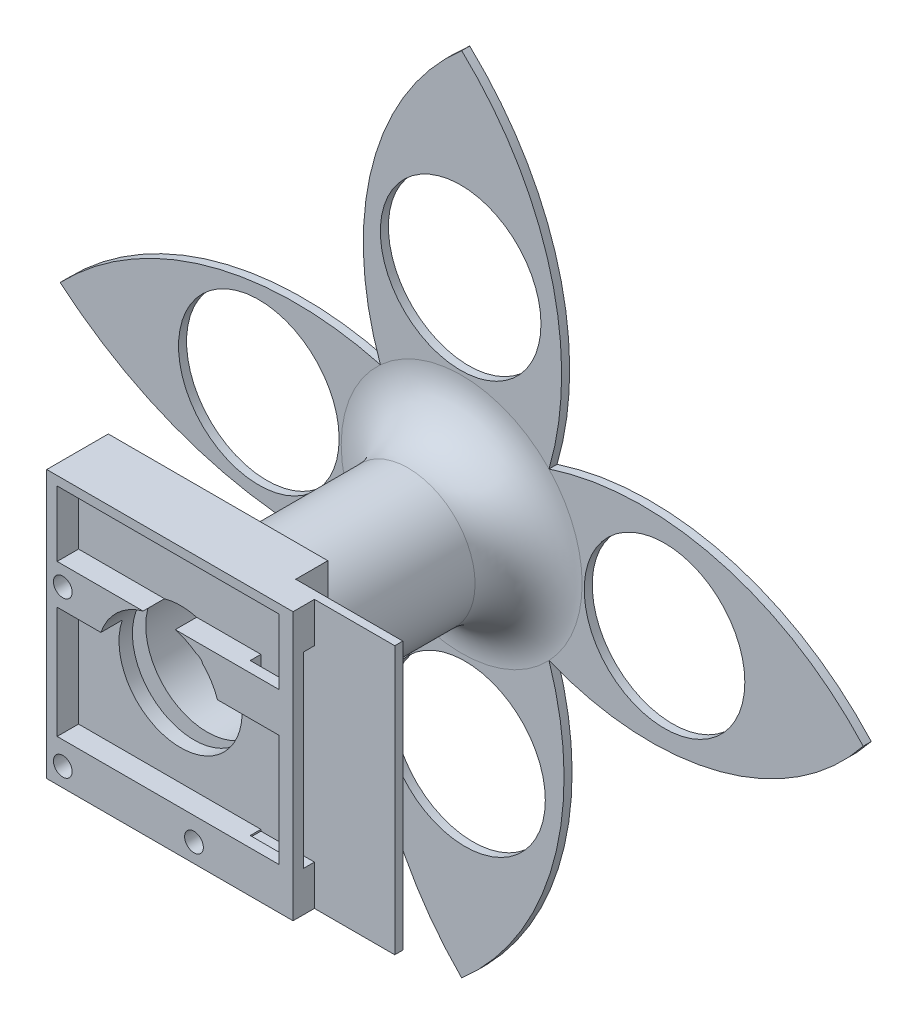
SolidWorks part; units mm, degrees
ref_plane "前视基准面" through (0, 0, 0) normal (0, 0, 1) x (1, 0, 0)
ref_plane "上视基准面" through (0, 0, 0) normal (0, 1, 0) x (1, 0, 0)
ref_plane "右视基准面" through (0, 0, 0) normal (1, 0, 0) x (0, 0, -1)
other "Configuration Table"
sketch "草图1" plane through (0, 0, 0) normal (0, 0, 1) x (1, 0, 0)
  circle A0 centre (0, 0) radius 150
extrude "凸台-拉伸1" add sketch "草图1" along normal blind 3
sketch "草图2" plane through (0, 0, 3) normal (0, 0, 1) x (1, 0, 0)
  circle A0 centre (0, 0) radius 25
extrude "凸台-拉伸2" add sketch "草图2" along normal blind 90
sketch "草图4" plane through (0, 0, 93) normal (0, 0, 1) x (1, 0, 0)
  line L3 (-40, -40) -> (40, -40)
  line L6 (40, 40) -> (-40, 40)
  line L7 (-40, 40) -> (-40, -40)
  line L8 (40, 40) -> (40, -40)
extrude "凸台-拉伸3" add sketch "草图4" along normal blind 5
sketch "草图5" plane through (0, 0, 98) normal (0, 0, 1) x (1, 0, 0)
  line L0 (-40, -40) -> (-40, -36)
  line L5 (-40, -36) -> (40, -36)
  line L16 (-40, 40) -> (-40, 36)
  line L17 (-40, 40) -> (-40, -40) construction
  line L18 (-40, 36) -> (40, 36)
  line L19 (40, 36) -> (40, 40)
  line L20 (40, 40) -> (-40, 40)
  line L21 (40, -36) -> (40, -40)
  line L22 (40, -40) -> (-40, -40)
extrude "凸台-拉伸4" add sketch "草图5" along normal blind 5
sketch "草图6" plane through (0, 0, 103) normal (0, 0, 1) x (1, 0, 0)
  line L1 (-40, 40) -> (40, 40)
  line L2 (-40, 40) -> (-40, -40)
  line L3 (-40, -40) -> (40, -40)
  line L4 (40, 40) -> (40, -40)
extrude "凸台-拉伸5" add sketch "草图6" along normal blind 5
sketch "草图8" plane through (0, -40, 0) normal (0, -1, 0) x (1, 0, 0)
  line L6 (-40, 93) -> (40, 93)
  line L7 (40, 93) -> (40, 108)
  line L10 (40, 108) -> (-40, 108)
  line L11 (-40, 108) -> (-40, 93)
  line L12 (-40, 93) -> (40, 93)
  line L13 (40, 93) -> (40, 108)
  line L16 (40, 108) -> (-40, 108)
  line L17 (-40, 108) -> (-40, 93)
  dimension "D1" = 0
extrude "凸台-拉伸7" add sketch "草图8" along normal blind 10
sketch "草图9" plane through (0, 40, 0) normal (0, 1, 0) x (1, 0, 0)
  line L6 (40, -93) -> (-40, -93)
  line L7 (-40, -93) -> (-40, -108)
  line L8 (-40, -108) -> (40, -108)
  line L11 (40, -108) -> (40, -93)
  line L12 (40, -93) -> (-40, -93)
  line L13 (-40, -93) -> (-40, -108)
  line L14 (-40, -108) -> (40, -108)
  line L17 (40, -108) -> (40, -93)
  dimension "D1" = 0
extrude "凸台-拉伸8" add sketch "草图9" along normal blind 10
sketch "草图10" plane through (0, 0, 108) normal (0, 0, 1) x (1, 0, 0)
  line L2 (-40, -50) -> (-40, 50)
  line L5 (-40, -50) -> (50, -50)
  line L6 (50, -50) -> (50, 50)
  line L7 (-40, 50) -> (40, 50) construction
  line L8 (50, 50) -> (-40, 50)
extrude "凸台-拉伸9" add sketch "草图10" along normal blind 8
sketch "草图11" plane through (0, 0, 116) normal (0, 0, 1) x (1, 0, 0)
  circle A0 centre (-36, 15) radius 3.5
  circle A1 centre (-36, -43) radius 3.5
  circle A2 centre (13, 15) radius 3.5
  circle A3 centre (13, -43) radius 3.5
extrude "切除-拉伸1" cut sketch "草图11" against normal blind 9
sketch "草图12" plane through (-40, 0, 0) normal (-1, 0, 0) x (0, 0, 1)
  line L0 (103, -36) -> (103, 36)
  line L1 (103, 36) -> (98, 36)
  line L2 (98, 36) -> (98, -36)
  line L3 (98, -36) -> (103, -36)
  line L4 (93, 50) -> (93, -50)
  line L5 (93, -50) -> (116, -50)
  line L6 (116, -50) -> (116, 50)
  line L7 (116, 50) -> (93, 50)
  line L8 (93, 50) -> (93, -50)
  line L9 (93, -50) -> (116, -50)
  line L10 (116, -50) -> (116, 50)
  line L11 (116, 50) -> (93, 50)
  dimension "D1" = 0
extrude "凸台-拉伸11" add sketch "草图12" along normal blind 2
sketch "草图17" plane through (0, 0, 3) normal (0, 0, 1) x (1, 0, 0)
  circle A0 centre (-75.7736, 1.5615) radius 30
  circle A1 centre (-0.3761, 76.3734) radius 30
  circle A2 centre (75.7702, -1.4084) radius 30
  circle A3 centre (1.2423, -76.8609) radius 30
extrude "切除-拉伸5" cut sketch "草图17" against normal blind 10 contours A1 | A0 | A2 | A3
sketch "草图18" plane through (0, 0, 116) normal (0, 0, 1) x (1, 0, 0)
  line L1 (-38.1119, 46.6223) -> (44.7722, 46.6223)
  line L2 (-38.1119, 46.6223) -> (-38.1119, 22.2011)
  line L3 (-38.1119, 22.2011) -> (44.7722, 22.2011)
  line L4 (44.7722, 46.6223) -> (44.7722, 22.2011)
  line L5 (-38.1119, 7.4004) -> (44.7722, 7.4004)
  line L6 (-38.1119, 7.4004) -> (-38.1119, -34.4117)
  line L7 (-38.1119, -34.4117) -> (44.7722, -34.4117)
  line L8 (44.7722, 7.4004) -> (44.7722, -34.4117)
extrude "切除-拉伸6" cut sketch "草图18" against normal blind 8
sketch "草图20" plane through (0, 0, 0) normal (0, 0, -1) x (-1, 0, 0)
  circle A0 centre (0, 0) radius 23
extrude "切除-拉伸7" cut sketch "草图20" against normal blind 120
sketch "草图21" plane through (40, 0, 0) normal (1, 0, 0) x (0, 0, -1)
  line L0 (-93, -50) -> (-108, -50) construction
  line L1 (-108, 50) -> (-105, 50)
  line L2 (-108, 50) -> (-108, -50)
  line L3 (-108, -50) -> (-105, -50)
  line L4 (-105, 50) -> (-105, -50)
extrude "凸台-拉伸12" add sketch "草图21" along normal blind 40
sketch "草图22" plane through (50, 0, 0) normal (1, 0, 0) x (0, 0, -1)
  line L1 (-108, -50) -> (-108, 50) construction
  line L3 (-108, 35) -> (-112, 35)
  line L4 (-108, 35) -> (-108, -35)
  line L5 (-108, -35) -> (-112, -35)
  line L6 (-112, 35) -> (-112, -35)
extrude "切除-拉伸8" cut sketch "草图22" against normal blind 20
fillet "圆角1" radius 20 3 edges at (25, 0, 3) (40, 0, 103) (25, 0, 93)
sketch "草图24" plane through (0, 0, 3) normal (0, 0, 1) x (1, 0, 0)
  circle A0 centre (0, 0) radius 150
  arc A1 (-150, 0) -> (-30.3649, 33.2111) centre (-62.0429, -84.7608) cw
  circle A2 centre (0, 0) radius 45 construction
  arc A3 (-150, 0) -> (-30.3649, -33.2111) centre (-54.1008, 113.3702) ccw
  arc A4 (0, -150) -> (-30.3649, -33.2111) centre (84.7889, -65.6132) cw
  arc A5 (32.6317, -30.9867) -> (0, -150) centre (-73.2295, -65.9413) cw
  arc A6 (150, 0) -> (32.6317, -30.9867) centre (70.5742, 63.0698) cw
  arc A7 (32.6317, 30.9867) -> (150, 0) centre (67.509, -74.68) cw
  arc A8 (32.6317, 30.9867) -> (0, 150) centre (-80.4282, 63.9675) ccw
  arc A9 (-30.3649, 33.2111) -> (0, 150) centre (69.6951, 69.5376) cw
  circle M6 centre (0, 0) radius 150
extrude "切除-拉伸9" cut sketch "草图24" against normal blind 10 contours A1 A9 A0 | A8 A7 M6 | A0 A6 A5 | A4 A3 M6 region at (78.8341, 78.8525, 3) region at (79.0323, -79.6183, 3) region at (-79.1178, 78.6143, 3) region at (-78.5256, -77.5536, 3)
